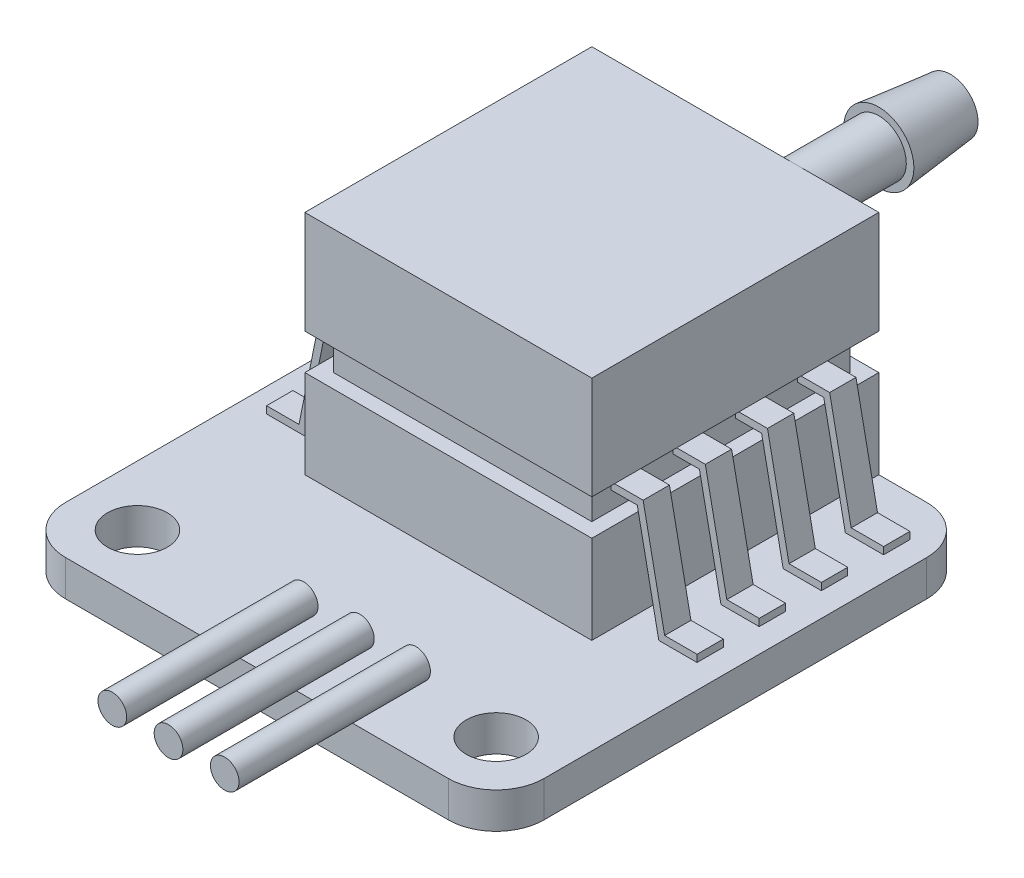
SolidWorks part; units mm, degrees
ref_plane "Спереди" through (0, 0, 0) normal (0, 0, 1) x (1, 0, 0)
ref_plane "Сверху" through (0, 0, 0) normal (0, 1, 0) x (1, 0, 0)
ref_plane "Справа" through (0, 0, 0) normal (1, 0, 0) x (0, 0, -1)
sketch "Эскиз1" plane through (0, 0, 0) normal (0, 1, 0) x (1, 0, 0)
  line L0 (2.5, 2.5) -> (17.5, 2.5) construction
  line L1 (2, 0) -> (18, 0)
  line L2 (0, 2) -> (0, 18)
  line L3 (2, 20) -> (18, 20)
  line L4 (20, 2) -> (20, 18)
  line L5 (10, 2.5) -> (10, 0) construction
  circle A0 centre (2.5, 2.5) radius 1.25
  circle A1 centre (17.5, 2.5) radius 1.25
  arc A2 (20, 2) -> (18, 0) centre (18, 2) cw
  arc A3 (2, 0) -> (0, 2) centre (2, 2) cw
  arc A4 (0, 18) -> (2, 20) centre (2, 18) cw
  arc A5 (18, 20) -> (20, 18) centre (18, 18) cw
  point P13 (0, 0)
  dimension "D3" = 2
  dimension "D5" = 2.5
  dimension "D1" = 20
  dimension "D2" = 20
  dimension "D4" = 15
  dimension "D6" = 2.5
extrude "Бобышка-Вытянуть1" add sketch "Эскиз1" along normal blind 1.5
sketch "Эскиз2" plane through (0, 1.5, 0) normal (0, 1, 0) x (1, 0, 0)
  line L0 (18, 20) -> (2, 20) construction
  line L1 (4, 20) -> (16, 20)
  line L2 (4, 20) -> (4, 8)
  line L3 (4, 8) -> (16, 8)
  line L4 (16, 20) -> (16, 8)
  line L5 (10, 20) -> (10, 8) construction
  dimension "D1" = 12
  dimension "D2" = 12
extrude "Бобышка-Вытянуть2" add sketch "Эскиз2" along normal blind 9.5
sketch "Эскиз3" plane through (0, 1.5, 0) normal (0, 1, 0) x (1, 0, 0)
  line L4 (10, 8) -> (10, 20) construction
  line L5 (15.4, 19.4) -> (4.6, 19.4)
  line L6 (15.4, 19.4) -> (15.4, 8.6)
  line L7 (15.4, 8.6) -> (4.6, 8.6)
  line L8 (4.6, 19.4) -> (4.6, 8.6)
  line L9 (4, 8) -> (16, 8) construction
  line L10 (16, 20) -> (4, 20) construction
  line L11 (4.6, 19.4) -> (15.4, 8.6) construction
  point P10 (10, 14)
  point P11 (10, 14)
  dimension "D1" = 10.8
  dimension "D2" = 10.8
extrude "Вырез-Вытянуть1" cut sketch "Эскиз3" along normal blind 1.5 from offset 3.7 flip side to cut
sketch "Эскиз4" plane through (0, 0, -20) normal (0, 0, -1) x (-1, 0, 0)
  line L0 (-16, 11) -> (-16, 6.7) construction
  line L1 (-16, 11) -> (-4, 11) construction
  line L2 (-4, 1.5) -> (-2, 1.5) construction
  line L3 (-4, 5.2) -> (-4, 1.5) construction
  circle A0 centre (-12.5, 9.85) radius 1.15
  circle A1 centre (-7.5, 2.65) radius 1.15
  circle A2 centre (-12.5, 9.85) radius 0.6
  circle A3 centre (-7.5, 2.65) radius 0.6
  dimension "D2" = 2.3
  dimension "D4" = 1.2
  dimension "D1" = 3.5
  dimension "D3" = 3.5
extrude "Бобышка-Вытянуть3" add sketch "Эскиз4" along normal blind 6.5
sketch "Эскиз5" plane through (0, 0, -26.5) normal (0, 0, -1) x (-1, 0, 0)
  circle A1 centre (-7.5, 2.65) radius 1.15 construction
  circle A2 centre (-7.5, 2.65) radius 1.15
  circle A3 centre (-12.5, 9.85) radius 1.15 construction
  circle A4 centre (-12.5, 9.85) radius 1.15
  circle A5 centre (-12.5, 9.85) radius 0.6 construction
  circle A6 centre (-12.5, 9.85) radius 0.6
  circle A7 centre (-7.5, 2.65) radius 0.6 construction
  circle A8 centre (-7.5, 2.65) radius 0.6
extrude "Бобышка-Вытянуть4" add sketch "Эскиз5" against normal blind 3 draft 6 draft outward yes
sketch "Эскиз6" plane through (0, 0, -20) normal (0, 0, -1) x (-1, 0, 0)
  line L0 (-17.4, 1.5) -> (-19, 1.5)
  line L1 (-18, 1.5) -> (-16, 1.5) construction
  line L2 (-17.4, 1.5) -> (-16.5, 5.95)
  line L3 (-16.5, 5.95) -> (-15.4, 5.95)
  line L4 (-10, 5.2) -> (-10, 1.5) construction
  line L5 (-16, 5.2) -> (-4, 5.2) construction
  line L6 (-3.5, 5.95) -> (-4.6, 5.95)
  line L7 (-2.6, 1.5) -> (-3.5, 5.95)
  line L8 (-2.6, 1.5) -> (-1, 1.5)
  line L9 (-15.4, 6.7) -> (-15.4, 5.2) construction
  dimension "D1" = 13
  dimension "D2" = 14.8
  dimension "D3" = 18
extrude "Вытянуть-Тонкостенный1" add sketch "Эскиз6" against normal blind 1.1 from offset 1.7 thin offset against normal yes thin type one direction reverse wall 0.3
pattern_linear "Линейный массив1" count 4 spacing 2.6 along (0, 0, 1) of "Вытянуть-Тонкостенный1"
sketch "Эскиз7" plane through (0, 0, 0) normal (0, 0, 1) x (1, 0, 0)
  line L0 (8.95, 2) -> (13.65, 2) construction
  line L1 (2, 1.5) -> (18, 1.5) construction
  line L2 (20, 1.5) -> (20, 0) construction
  circle A0 centre (8.95, 2) radius 0.6
  circle A1 centre (11.3, 2) radius 0.6
  circle A2 centre (13.65, 2) radius 0.6
  dimension "D1" = 1.2
  dimension "D2" = 0.5
  dimension "D3" = 4.7
  dimension "D4" = 8.7
extrude "Бобышка-Вытянуть5" add sketch "Эскиз7" along normal blind 5 and the other way blind 3
